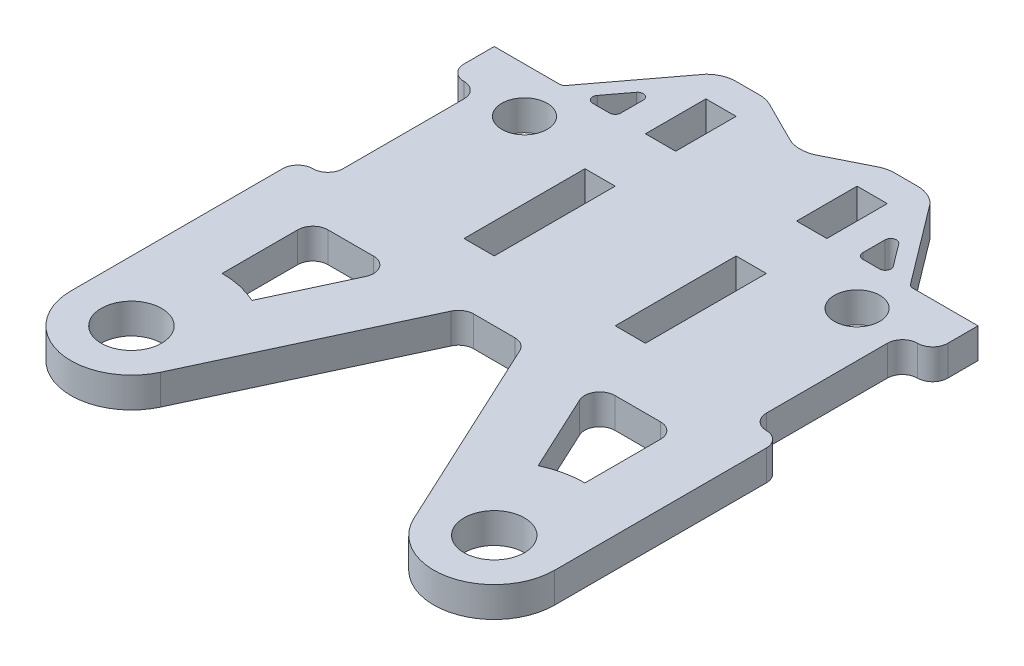
SolidWorks part; units mm, degrees
ref_plane "Front Plane" through (0, 0, 0) normal (0, 0, 1) x (1, 0, 0)
ref_plane "Top Plane" through (0, 0, 0) normal (0, 1, 0) x (1, 0, 0)
ref_plane "Right Plane" through (0, 0, 0) normal (1, 0, 0) x (0, 0, -1)
sketch "Sketch1" plane through (0, 0, 0) normal (0, 1, 0) x (1, 0, 0)
  line L0 (0, 12.7) -> (0, -12.7) construction
  line L1 (25.4, -12.7) -> (23.8125, -12.7)
  line L2 (25.4, -12.7) -> (25.4, -9.525)
  line L3 (25.4, 12.7) -> (23.8125, 12.7)
  line L4 (-25.4, -12.7) -> (-25.4, -9.525)
  line L5 (-25.4, -31.75) -> (-25.4, -12.7)
  line L6 (-6.35, 6.35) -> (-9.525, 6.35)
  line L7 (-6.35, 6.35) -> (-6.35, -6.35)
  line L8 (-6.35, -6.35) -> (-9.525, -6.35)
  line L9 (-9.525, 6.35) -> (-9.525, -6.35)
  line L10 (-3.175, -12.7) -> (-13.2935, -34.4304)
  line L11 (-19.05, -12.7) -> (-19.05, -22.225)
  line L12 (-15.0293, -23.1152) -> (-10.1796, -12.7)
  line L13 (-10.1796, -12.7) -> (-19.05, -12.7)
  line L14 (25.4, 0) -> (-25.4, 0) construction
  line L15 (-22.225, 6.35) -> (-22.225, -6.35)
  line L16 (-23.8125, 12.7) -> (-23.8125, -18.6877) construction
  line L17 (-25.4, 9.525) -> (-25.4, 12.7)
  line L18 (23.8125, 12.7) -> (23.8125, -18.6877) construction
  line L19 (25.4, 9.525) -> (25.4, 12.7)
  line L20 (22.225, 6.35) -> (22.225, -6.35)
  line L21 (10.1796, -12.7) -> (19.05, -12.7)
  line L22 (15.0293, -23.1152) -> (10.1796, -12.7)
  line L23 (19.05, -12.7) -> (19.05, -22.225)
  line L24 (3.175, -12.7) -> (13.2935, -34.4304)
  line L25 (9.525, 6.35) -> (9.525, -6.35)
  line L26 (6.35, -6.35) -> (9.525, -6.35)
  line L27 (6.35, 6.35) -> (6.35, -6.35)
  line L28 (6.35, 6.35) -> (9.525, 6.35)
  line L29 (25.4, -31.75) -> (25.4, -12.7)
  line L30 (25.4, -12.7) -> (25.4, -9.525)
  line L31 (25.4, 9.525) -> (25.4, 12.7)
  line L32 (3.175, -12.7) -> (-3.175, -12.7)
  line L33 (-6.35, 22.225) -> (-9.525, 22.225)
  line L34 (-6.35, 12.7) -> (-9.525, 12.7)
  line L35 (-6.35, 12.7) -> (-6.35, 19.05)
  line L36 (-6.35, 19.05) -> (-9.525, 19.05)
  line L37 (-9.525, 12.7) -> (-9.525, 19.05)
  line L38 (-23.8125, 12.7) -> (-18.2563, 12.7)
  line L39 (-6.35, 22.225) -> (0, 19.05)
  line L40 (16.2674, 12.7) -> (12.7, 12.7)
  line L41 (12.7, 17.4273) -> (16.2674, 12.7)
  line L42 (11.7701, 21.2951) -> (18.2563, 12.7)
  line L43 (6.35, 12.7) -> (9.525, 12.7)
  line L44 (-12.7, 12.7) -> (-12.7, 17.4273)
  line L45 (12.7, 12.7) -> (12.7, 17.4273)
  line L46 (-23.8125, 12.7) -> (-25.4, 12.7)
  line L47 (-6.35, 12.7) -> (-9.525, 12.7)
  line L48 (23.8125, 12.7) -> (18.2563, 12.7)
  line L49 (-11.7701, 21.2951) -> (-18.2563, 12.7)
  line L50 (-12.7, 17.4273) -> (-16.2674, 12.7)
  line L51 (-16.2674, 12.7) -> (-12.7, 12.7)
  line L52 (-10.5029, 20.3388) -> (-16.9891, 11.7437) construction
  line L53 (9.525, 12.7) -> (9.525, 19.05)
  line L54 (6.35, 12.7) -> (6.35, 19.05)
  line L55 (6.35, 12.7) -> (9.525, 12.7)
  line L56 (6.35, 22.225) -> (0, 19.05)
  line L57 (6.35, 19.05) -> (9.525, 19.05)
  line L58 (6.35, 22.225) -> (9.525, 22.225)
  circle A0 centre (-19.05, -31.75) radius 3.175
  arc A1 (-25.4, -31.75) -> (-13.2935, -34.4304) centre (-19.05, -31.75) ccw
  arc A2 (-15.0293, -23.1152) -> (-19.05, -22.225) centre (-19.05, -31.75) ccw
  circle A3 centre (-19.05, -31.75) radius 6.35 construction
  arc A4 (-23.8125, -7.9375) -> (-25.4, -9.525) centre (-23.8125, -9.525) ccw
  circle A5 centre (-19.05, -31.75) radius 9.525 construction
  arc A6 (-23.8125, -7.9375) -> (-22.225, -6.35) centre (-23.8125, -6.35) ccw
  arc A7 (-23.8125, 7.9375) -> (-22.225, 6.35) centre (-23.8125, 6.35) cw
  arc A8 (-23.8125, 7.9375) -> (-25.4, 9.525) centre (-23.8125, 9.525) cw
  arc A9 (23.8125, 7.9375) -> (25.4, 9.525) centre (23.8125, 9.525) ccw
  arc A10 (23.8125, 7.9375) -> (22.225, 6.35) centre (23.8125, 6.35) ccw
  arc A11 (23.8125, -7.9375) -> (22.225, -6.35) centre (23.8125, -6.35) cw
  arc A12 (23.8125, -7.9375) -> (25.4, -9.525) centre (23.8125, -9.525) cw
  arc A13 (15.0293, -23.1152) -> (19.05, -22.225) centre (19.05, -31.75) cw
  arc A14 (25.4, -31.75) -> (13.2935, -34.4304) centre (19.05, -31.75) cw
  circle A15 centre (19.05, -31.75) radius 3.175
  arc A16 (-11.7701, 21.2951) -> (-9.525, 22.225) centre (-9.525, 19.05) cw
  arc A17 (11.7701, 21.2951) -> (9.525, 22.225) centre (9.525, 19.05) ccw
  point P17 (-12.7, -31.75)
  point P21 (-9.525, -31.75)
  dimension "D7" = 6.35
  dimension "D1" = 50.8
  dimension "D2" = 25.4
  dimension "D3" = 3.175
  dimension "D4" = 12.7
  dimension "D5" = 6.35
  dimension "D6" = 6.35
  dimension "D8" = 44.45
  dimension "D9" = 19.05
  dimension "D11" = 3.175
  dimension "D13" = 6.35
  dimension "D14" = 6.35
  dimension "D15" = 3.175
  dimension "D16" = 1.5875
  dimension "D17" = 9.525
  dimension "D18" = 6.35
  dimension "D19" = 3.175
  dimension "D10" = 3.175
  dimension "D12" = 6.35
  dimension "D22" = 1.5875
extrude "Boss-Extrude1" add sketch "Sketch1" along normal blind 3.175 contours A14 L29 L2 A12 A11 L20 A10 A9 L19 L3 L17 A8 A7 L15 A6 A4 L4 L5 A1 L10 L32 L24 L12 A2 L11 L13 L27 L28 L25 L26 L9 L6 L7 L8 A0 A13 L22 L21 L23 A15 region at (0, 0, 5.8577)
fillet "Fillet1" radius 1.5875 6 edges at (19.05, 1.5875, 12.7) (10.1796, 1.5875, 12.7) (3.175, 1.5875, 12.7) (-3.175, 1.5875, 12.7) (-10.1796, 1.5875, 12.7) (-19.05, 1.5875, 12.7)
sketch "Sketch2" plane through (0, 3.175, 0) normal (0, 1, 0) x (1, 0, 0)
  line L0 (25.4, 12.7) -> (18.2563, 12.7) construction
  line L1 (-22.225, 6.35) -> (-22.225, -6.35) construction
  circle A0 centre (-17.4625, 7.9375) radius 2.3813
  circle A1 centre (17.4625, 7.9375) radius 2.3813
  dimension "D1" = 4.7625
  dimension "D2" = 4.7625
  dimension "D3" = 4.7625
extrude "Cut-Extrude1" cut sketch "Sketch2" against normal through all
fillet "Fillet2" radius 3.175 3 edges at (6.35, 1.5875, -22.225) (0, 1.5875, -19.05) (-6.35, 1.5875, -22.225)
fillet "Fillet4" radius 0.6 8 edges at (12.7, 1.5875, -12.7) (12.7, 1.5875, -17.4273) (-12.7, 1.5875, -17.4273) (-16.2674, 1.5875, -12.7) (-12.7, 1.5875, -12.7) (18.2563, 1.5875, -12.7) (16.2674, 1.5875, -12.7) (-18.2563, 1.5875, -12.7)
